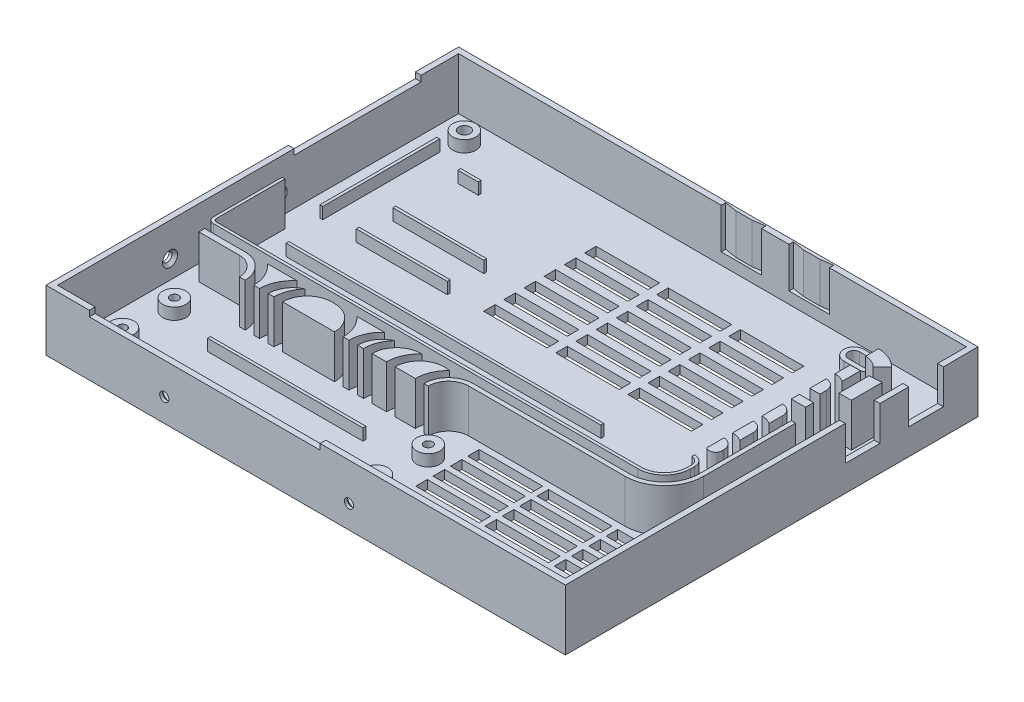
SolidWorks part; units mm, degrees
ref_plane "Front Plane" through (0, 0, 0) normal (0, 0, 1) x (1, 0, 0)
ref_plane "Top Plane" through (0, 0, 0) normal (0, 1, 0) x (1, 0, 0)
ref_plane "Right Plane" through (0, 0, 0) normal (1, 0, 0) x (0, 0, -1)
sketch "Sketch1" plane through (0, 0, 0) normal (0, 1, 0) x (1, 0, 0)
  line L0 (-67.5, 0) -> (67.5, 0) construction
  line L1 (0, 38) -> (0, -38) construction
  line L3 (-67.5, 38) -> (67.5, 38) construction
  line L4 (-67.5, 38) -> (-67.5, -38) construction
  line L5 (-67.5, -38) -> (67.5, -38) construction
  line L6 (67.5, 38) -> (67.5, -38) construction
  line L7 (-67.5, 38) -> (67.5, -38) construction
  line L8 (-67.5, -38) -> (67.5, 38) construction
  line L9 (-71, -71.5) -> (24, -71.5) construction
  line L10 (-23.5, -59) -> (-23.5, -84) construction
  line L11 (-38, -59) -> (-38, -71.5) construction
  line L12 (-17, -59) -> (-17, -71.5) construction
  line L13 (11, -59) -> (11, -71.5) construction
  line L14 (-79.5, 48) -> (-79.5, -95) construction
  line L16 (24, -59) -> (24, -84) construction
  line L17 (-79.5, -95) -> (100.5, -95) construction
  line L18 (100.5, -95) -> (100.5, 48) construction
  line L19 (-71, -59) -> (-71, -84) construction
  line L20 (-71, -84) -> (24, -84) construction
  line L21 (100.5, 48) -> (-79.5, 48) construction
  line L22 (-71, -59) -> (24, -59) construction
  line L23 (0, 38) -> (0, 42) construction
  line L24 (-71.5, 42) -> (71.5, 42) construction
  line L25 (-71.5, 42) -> (-71.5, -42) construction
  line L26 (-71.5, -42) -> (71.5, -42) construction
  line L27 (71.5, 42) -> (71.5, -42) construction
  line L28 (-67.5, 0) -> (-71.5, 0) construction
  line L29 (-43, -59) -> (-43, -71.5) construction
  line L30 (-48, -59) -> (-48, -71.5) construction
  line L31 (-12, -59) -> (-12, -71.5) construction
  line L32 (-7, -59) -> (-7, -71.5) construction
  line L33 (1, -59) -> (1, -71.5) construction
  line L34 (67.5, 38) -> (72.7, 38) construction
  line L35 (67.5, 40) -> (72.7, 40)
  line L36 (67.5, 36) -> (72.7, 36)
  line L37 (67.5, -38) -> (72.6846, -38.4) construction
  line L40 (67.6538, -36.0059) -> (72.8384, -36.4059)
  line L41 (67.3462, -39.9941) -> (72.5307, -40.3941)
  line L42 (-67.5, -38) -> (-67.5, -38.4) construction
  line L43 (-65.5, -38) -> (-65.5, -38.4)
  line L44 (-69.5, -38) -> (-69.5, -38.4)
  circle A0 centre (-67.5, 38) radius 2
  circle A4 centre (-67.5, -62.5) radius 1.5
  circle A8 centre (20.5, -62.5) radius 1.5
  circle A9 centre (20.5, -80.5) radius 1.5
  circle A10 centre (-67.5, -80.5) radius 1.5
  arc A11 (67.5, 40) -> (67.5, 36) centre (67.5, 38) ccw
  arc A12 (72.7, 36) -> (72.7, 40) centre (72.7, 38) ccw
  arc A15 (67.6538, -36.0059) -> (67.3462, -39.9941) centre (67.5, -38) ccw
  arc A16 (72.5307, -40.3941) -> (72.8384, -36.4059) centre (72.6846, -38.4) ccw
  arc A17 (-65.5, -38) -> (-69.5, -38) centre (-67.5, -38) ccw
  arc A18 (-69.5, -38.4) -> (-65.5, -38.4) centre (-67.5, -38.4) ccw
  point P5 (0, 0)
  point P11 (70.1, 38)
  point P13 (-67.5, -38.2)
  point P14 (-23.5, -70)
  point P27 (0, 0)
  point P62 (70.0923, -38.2)
  dimension "D3" = 4
  dimension "D6" = 84
  dimension "D1" = 76
  dimension "D2" = 135
  dimension "D4" = 18
  dimension "D5" = 88
  dimension "D7" = 143
  dimension "D8" = 25
  dimension "D9" = 95
  dimension "D10" = 17
  dimension "D11" = 28
  dimension "D12" = 33
  dimension "D13" = 54
  dimension "D14" = 82
  dimension "D15" = 14.5
  dimension "D16" = 10
  dimension "D17" = 12
  dimension "D18" = 33
  dimension "D19" = 23
  dimension "D20" = 59
  dimension "D21" = 64
  dimension "D22" = 72
  dimension "D23" = 5.2
  dimension "D24" = 4
  dimension "D25" = 4
  dimension "D26" = 5.2
  dimension "D27" = 4
  dimension "D28" = 0.4
  dimension "D29" = 0.4
sketch "CablePath" plane through (0, 0, 0) normal (0, 1, 0) x (1, 0, 0)
  line L0 (-12, -59) -> (-12, -56) construction
  line L5 (101, -94.5) -> (101, 47)
  line L6 (101, 47) -> (-79, 47)
  line L8 (-43, -56) -> (-43, -70.139) construction
  line L9 (-75.5, -42.5222) -> (-75.5, -18.6789) construction
  line L12 (71.5, -29) -> (80.8048, -29) construction
  line L16 (-71.5, -42) -> (71.5, -42) construction
  line L18 (71.5, -18.84) -> (80.8048, -18.84) construction
  line L21 (80.8048, -51.7714) -> (80.8048, 34.0145) construction
  line L22 (30.5, -56) -> (-60.9203, -56) construction
  line L23 (-10.5, -56) -> (-8.5, -56)
  line L24 (71.5, 40.5) -> (71.5, -42) construction
  line L25 (1, -59) -> (1, -56) construction
  line L26 (85.8048, -3.52) -> (85.8048, -35.359) construction
  line L27 (-79, 47) -> (-79, -94.5)
  line L28 (11, -59) -> (11, -56) construction
  line L29 (-79, -94.5) -> (101, -94.5)
  line L30 (-38, -70.139) -> (-38, -56) construction
  line L31 (-43, -59) -> (-43, -71.5) construction
  line L32 (-38, -59) -> (-38, -71.5) construction
  line L33 (71.5, 1.48) -> (80.8048, 1.48) construction
  line L34 (-58, -44.5) -> (-72.0222, -44.5)
  line L35 (75.1637, -46) -> (-33, -46) construction
  line L36 (84.3048, -3.52) -> (84.3048, -8.2028)
  line L37 (-71, -59) -> (24, -59) construction
  line L38 (75.1637, -44.5) -> (-33, -44.5)
  line L39 (71.5, -8.68) -> (80.8048, -8.68) construction
  line L40 (87.3048, -3.52) -> (87.3048, -35.359)
  line L41 (21, -47.5) -> (75.1637, -47.5)
  line L42 (84.3048, -13.68) -> (84.3048, -18.3628)
  line L43 (84.3048, -23.84) -> (84.3048, -24.2165)
  line L44 (84.3048, -3.52) -> (84.3048, -35.359) construction
  line L45 (84.3048, -34) -> (84.3048, -35.359)
  line L46 (-27.8976, -47.4999) -> (-26.899, -47.4999)
  line L47 (75.1637, -47.5) -> (-33, -47.5) construction
  line L48 (2.5, -56) -> (9.5, -56)
  line L49 (-41.5, -56) -> (-39.5, -56)
  line L50 (-36.5, -56) -> (-18.5, -56)
  line L51 (-17, -59) -> (-17, -71.5) construction
  line L52 (21, -49) -> (75.1637, -49)
  line L53 (88.8048, -3.52) -> (88.8048, -35.359)
  line L54 (83.3048, -34) -> (83.3048, -35.359)
  line L55 (75.1637, -43.5) -> (-33, -43.5)
  line L56 (12.5, -56) -> (14, -56)
  line L57 (-58, -46) -> (-72.0222, -46) construction
  line L58 (80.8048, 2.98) -> (80.8048, 5.7849)
  line L59 (80.8048, -0.02) -> (80.8048, -7.18)
  line L60 (80.8048, -10.18) -> (80.8048, -17.34)
  line L61 (80.8048, -20.34) -> (80.8048, -26.2952)
  line L62 (80.8048, -30.5) -> (80.8048, -31.5)
  line L63 (-74, -42.5222) -> (-74, -18.6789)
  line L64 (80.8048, 5.7849) -> (85.7673, 5.7849)
  line L65 (85.7673, 5.7849) -> (85.7673, 2.98)
  line L66 (85.7673, 2.98) -> (80.8048, 2.98)
  line L67 (87.3048, -3.52) -> (88.8048, -3.52)
  line L68 (-7, -59) -> (-7, -56) construction
  line L69 (-17, -59) -> (-17, -56) construction
  line L70 (-48, -59) -> (-48, -56) construction
  line L71 (-58, -43.5) -> (-72.0222, -43.5)
  line L72 (-73, -42.5222) -> (-73, -18.6789)
  line L73 (11, -59) -> (11, -71.5) construction
  line L74 (-58, -47.5) -> (-72.0222, -47.5)
  line L75 (-58, -49.5) -> (-72.0222, -49.5)
  line L76 (-51.5, -56) -> (-49.5, -56)
  line L77 (-72.0222, -47.5) -> (-72.0222, -49.5)
  line L78 (-58, -43.5) -> (-33, -43.5)
  line L79 (-74, -18.6789) -> (-73, -18.6789)
  line L80 (-46.5, -56) -> (-44.5, -56)
  line L81 (-19.2537, -47.5) -> (-9.746, -47.5)
  line L82 (-40.38, -47.1804) -> (-50.62, -47.1804)
  line L83 (-58, -44.5) -> (-33, -44.5)
  line L84 (-15.5, -56) -> (-13.5, -56)
  line L85 (3, -47.5) -> (3.254, -47.5)
  line L86 (-5.5, -56) -> (-0.5, -56)
  line L87 (-71.5, 42) -> (-71.5, -42) construction
  line L88 (67.5, 16.6233) -> (80.8048, 16.6233) construction
  line L89 (67.5, 27.1917) -> (80.8048, 27.1917) construction
  line L90 (67.5, 6.7426) -> (83.9849, 6.7426) construction
  line L91 (85.8048, -3.52) -> (85.8048, 11.6233) construction
  line L92 (85.8048, 11.6233) -> (85.8048, 22.1917) construction
  line L93 (80.8048, 33.1917) -> (80.8048, 28.6917)
  line L94 (85.4191, 26.7697) -> (88.5829, 29.9699)
  line L95 (87.3048, 13.0166) -> (87.3048, 23.4421)
  line L96 (87.3048, 23.4421) -> (91.5804, 23.7236)
  line L97 (84.3065, 23.4421) -> (84.3055, 17.1)
  line L98 (84.3044, 9.4184) -> (80.8048, 9.4184)
  line L99 (80.8048, 9.4184) -> (80.8048, 15.1233)
  line L100 (84.3048, 11.6233) -> (84.3044, 9.4184)
  line L101 (80.8048, 18.1233) -> (80.8048, 23.4421)
  line L102 (91.5804, 23.7236) -> (91.5804, 13.0166)
  line L103 (91.5804, 13.0166) -> (87.3048, 13.0166)
  line L104 (84.3065, 23.4421) -> (80.8048, 23.4421)
  arc A0 (14, -56) -> (21, -49) centre (21, -56) cw
  circle A1 centre (-67.5, -62.5) radius 1.5 construction
  arc A2 (9.5, -56) -> (21, -44.5) centre (21, -56) cw construction
  arc A3 (75.1637, -49) -> (88.8048, -35.359) centre (75.1637, -35.359) ccw
  arc A4 (85.4191, 26.7697) -> (80.8048, 28.6917) centre (80.8048, 22.1917) ccw
  arc A5 (88.5829, 29.9699) -> (80.8048, 33.1917) centre (80.8048, 22.1917) ccw
  arc A7 (84.3055, 17.1) -> (80.8048, 18.1233) centre (80.8048, 11.6233) ccw
  circle A8 centre (-67.5, -80.5) radius 1.5 construction
  circle A9 centre (-67.5, -62.5) radius 1.5
  circle A10 centre (20.5, -62.5) radius 1.5 construction
  circle A11 centre (-67.5, -80.5) radius 1.5
  arc A12 (80.8048, -26.2952) -> (84.3048, -24.2165) centre (82.1448, -24.5655) ccw
  arc A13 (85.8048, 22.1917) -> (80.8048, 27.1917) centre (80.8048, 22.1917) ccw construction
  arc A14 (85.8048, 11.6233) -> (80.8048, 16.6233) centre (80.8048, 11.6233) ccw construction
  arc A15 (84.3048, 11.6233) -> (80.8048, 15.1233) centre (80.8048, 11.6233) ccw
  arc A16 (80.8048, 1.48) -> (85.8048, -3.52) centre (80.8048, -3.52) cw construction
  arc A17 (80.8048, -8.68) -> (85.8048, -13.68) centre (80.8048, -13.68) cw construction
  arc A18 (80.8048, -18.84) -> (85.8048, -23.84) centre (80.8048, -23.84) cw construction
  arc A19 (80.8048, -29) -> (85.8048, -34) centre (80.8048, -34) cw construction
  arc A20 (75.1637, -46) -> (85.8048, -35.359) centre (75.1637, -35.359) ccw construction
  arc A21 (-43, -56) -> (-33, -46) centre (-33, -56) cw construction
  arc A22 (-38, -56) -> (-27.8796, -46) centre (-27.9993, -56) cw construction
  arc A23 (1, -56) -> (11, -46) centre (11, -56) cw construction
  arc A24 (11, -56) -> (21, -46) centre (21, -56) cw construction
  circle A25 centre (20.5, -62.5) radius 1.5
  circle A26 centre (20.5, -80.5) radius 1.5 construction
  circle A27 centre (20.5, -80.5) radius 1.5
  arc A28 (80.8048, -0.02) -> (84.3048, -3.52) centre (80.8048, -3.52) cw
  arc A29 (75.1637, -44.5) -> (84.3048, -35.359) centre (75.1637, -35.359) ccw
  arc A30 (-44.5, -56) -> (-40.38, -47.1804) centre (-33, -56) cw
  arc A31 (80.8048, -10.18) -> (84.3048, -13.68) centre (80.8048, -13.68) cw
  arc A32 (80.8048, -20.34) -> (84.3048, -23.84) centre (80.8048, -23.84) cw
  arc A33 (80.8048, -30.5) -> (84.3048, -34) centre (80.8048, -34) cw
  arc A34 (12.5, -56) -> (21, -47.5) centre (21, -56) cw
  arc A35 (2.5, -56) -> (13, -47.7386) centre (11, -56) cw
  arc A36 (-36.5, -56) -> (-27.8976, -47.4999) centre (-27.9993, -56) cw
  arc A37 (80.8048, 2.98) -> (87.3048, -3.52) centre (80.8048, -3.52) cw construction
  arc A38 (75.1637, -47.5) -> (87.3048, -35.359) centre (75.1637, -35.359) ccw
  arc A39 (-41.5, -56) -> (-36.5004, -48.2542) centre (-33, -56) cw
  arc A40 (80.8048, -7.18) -> (84.3048, -8.2028) centre (80.8048, -13.68) cw
  arc A41 (80.8048, -17.34) -> (84.3048, -18.3628) centre (80.8048, -23.84) cw
  arc A43 (9.5, -56) -> (13, -47.7386) centre (21, -56) cw
  arc A44 (-0.5, -56) -> (3.254, -47.5) centre (11, -56) cw
  arc A45 (-39.5, -56) -> (-36.5004, -48.2542) centre (-27.9993, -56) cw
  arc A46 (-39.5, -56) -> (-27.8617, -44.5001) centre (-27.9993, -56) cw construction
  arc A47 (87.3048, 11.6233) -> (80.8048, 18.1233) centre (80.8048, 11.6233) ccw construction
  arc A48 (80.8048, -7.18) -> (87.3048, -13.68) centre (80.8048, -13.68) cw construction
  arc A49 (80.8048, -17.34) -> (87.3048, -23.84) centre (80.8048, -23.84) cw construction
  arc A50 (80.8048, 4.48) -> (88.8048, -3.52) centre (80.8048, -3.52) cw construction
  arc A51 (-0.5, -56) -> (11, -44.5) centre (11, -56) cw construction
  arc A52 (80.8048, -31.5) -> (83.3048, -34) centre (80.8048, -34) cw
  arc A53 (75.1637, -43.5) -> (83.3048, -35.359) centre (75.1637, -35.359) ccw
  arc A54 (-48, -56) -> (-58, -46) centre (-58, -56) ccw construction
  arc A55 (-17, -56) -> (-26.881, -46) centre (-27.0007, -56) ccw construction
  arc A56 (-41.5, -56) -> (-33, -47.5) centre (-33, -56) cw construction
  arc A57 (-45.5, -56) -> (-33, -43.5) centre (-33, -56) cw construction
  arc A58 (-72.0222, -46) -> (-75.5, -42.5222) centre (-72.0222, -42.5222) cw construction
  arc A59 (-46.5, -56) -> (-50.62, -47.1804) centre (-58, -56) ccw
  arc A60 (-72.0222, -44.5) -> (-74, -42.5222) centre (-72.0222, -42.5222) cw
  arc A61 (-15.5, -56) -> (-19.2537, -47.5) centre (-27.0007, -56) ccw
  arc A62 (-72.0222, -43.5) -> (-73, -42.5222) centre (-72.0222, -42.5222) cw
  arc A63 (-49.5, -56) -> (-58, -47.5) centre (-58, -56) ccw
  arc A64 (-51.5, -56) -> (-58, -49.5) centre (-58, -56) ccw
  arc A65 (-45.5, -56) -> (-58, -43.5) centre (-58, -56) ccw construction
  arc A66 (-18.5, -56) -> (-26.899, -47.4999) centre (-27.0007, -56) ccw
  arc A67 (-12, -56) -> (-2, -46) centre (-2, -56) cw construction
  arc A68 (-15.5, -56) -> (-26.8631, -44.5001) centre (-27.0007, -56) ccw construction
  arc A69 (-46.5, -56) -> (-58, -44.5) centre (-58, -56) ccw construction
  arc A70 (-44.5, -56) -> (-33, -44.5) centre (-33, -56) cw construction
  arc A71 (2.5, -56) -> (11, -47.5) centre (11, -56) cw construction
  arc A72 (-7, -56) -> (3, -46) centre (3, -56) cw construction
  arc A73 (-10.5, -56) -> (-5.5, -48.254) centre (-2, -56) cw
  arc A74 (-5.5, -56) -> (3, -47.5) centre (3, -56) cw
  arc A75 (-13.5, -56) -> (-9.746, -47.5) centre (-2, -56) cw
  arc A76 (-8.5, -56) -> (-5.5, -48.254) centre (3, -56) cw
  arc A77 (87.3048, 22.1917) -> (80.8048, 28.6917) centre (80.8048, 22.1917) ccw construction
  arc A78 (-13.5, -56) -> (-2, -44.5) centre (-2, -56) cw construction
  arc A79 (-10.5, -56) -> (-2, -47.5) centre (-2, -56) cw construction
  arc A80 (91.8048, 22.1917) -> (80.8048, 33.1917) centre (80.8048, 22.1917) ccw construction
  arc A81 (-8.5, -56) -> (3, -44.5) centre (3, -56) cw construction
  point P0 (67.5, -38)
  point P7 (67.5, 38)
  point P10 (-67.5, -80.5)
  point P117 (77.6351, -51.5)
  point P118 (-14.035, -51.5)
  point P127 (77.6351, -54.5)
  point P128 (-14.035, -54.5)
  point P132 (79.6209, -33.364)
  point P134 (85.4849, -33.364)
  point P137 (3.3488, -47.5)
  point P138 (3.3488, -61)
  point P139 (-10.1512, -61)
  point P146 (3.3488, -50.5)
  point P147 (3.3488, -61)
  point P148 (-7.1512, -61)
  point P154 (80.8048, 22.2244)
  point P242 (3.4721, -55.4721)
  point P243 (-8, -55.4721)
  point P244 (3.4721, -44)
  point P253 (87.3048, 22.2244)
  point P256 (80.8048, 22.2244)
  point P257 (91.8048, 22.2244)
  dimension "D5" = 10.16
  dimension "D8" = 3
  dimension "D23" = 1.5
  dimension "D24" = 5
  dimension "D25" = 5
  dimension "D1" = 1.5
  dimension "D3" = 4
  dimension "D4" = 13
  dimension "D6" = 10.16
  dimension "D7" = 10.16
  dimension "D9" = 3.5
  dimension "D10" = 1.5
  dimension "D11" = 1.5
  dimension "D12" = 1
  dimension "D13" = 1.5
  dimension "D14" = 1
  dimension "D15" = 1.5
  dimension "D16" = 2
  dimension "D17" = 1.5
  dimension "D18" = 1.5
  dimension "D28" = 180
  dimension "D19" = 1.5
  dimension "D20" = 1.5
  dimension "D21" = 1.5
  dimension "D22" = 1.5
  dimension "D26" = 1.5
  dimension "D27" = 6
  dimension "D30" = 1.5
  dimension "D31" = 1.5
sketch "Bottom" plane through (0, 0, 0) normal (0, 1, 0) x (1, 0, 0)
  line L0 (-79.5, 48) -> (-79.5, -95) construction
  line L1 (-79.5, 48) -> (-79.5, -95)
  line L2 (-79.5, -95) -> (100.5, -95) construction
  line L3 (-79.5, -95) -> (100.5, -95)
  line L4 (67.6538, -36.0059) -> (72.8384, -36.4059) construction
  line L5 (67.3462, -39.9941) -> (72.5307, -40.3941) construction
  line L6 (100.5, -95) -> (100.5, 48) construction
  line L7 (100.5, -95) -> (100.5, 48)
  line L8 (100.5, 48) -> (-79.5, 48) construction
  line L9 (100.5, 48) -> (-79.5, 48)
  line L10 (67.6538, -36.0059) -> (72.8384, -36.4059)
  line L11 (67.3462, -39.9941) -> (72.5307, -40.3941)
  line L12 (67.5, 36) -> (72.7, 36) construction
  line L13 (67.5, 40) -> (72.7, 40) construction
  line L14 (67.5, 36) -> (72.7, 36)
  line L15 (67.5, 40) -> (72.7, 40)
  line L16 (-65.5, -38) -> (-65.5, -38.4) construction
  line L17 (-69.5, -38) -> (-69.5, -38.4) construction
  line L18 (-65.5, -38) -> (-65.5, -38.4)
  line L19 (-69.5, -38) -> (-69.5, -38.4)
  arc A0 (72.5307, -40.3941) -> (72.8384, -36.4059) centre (72.6846, -38.4) ccw construction
  arc A1 (67.6538, -36.0059) -> (67.3462, -39.9941) centre (67.5, -38) ccw construction
  arc A2 (72.5307, -40.3941) -> (72.8384, -36.4059) centre (72.6846, -38.4) ccw
  arc A3 (67.6538, -36.0059) -> (67.3462, -39.9941) centre (67.5, -38) ccw
  arc A4 (72.7, 36) -> (72.7, 40) centre (72.7, 38) ccw construction
  arc A5 (67.5, 40) -> (67.5, 36) centre (67.5, 38) ccw construction
  arc A6 (72.7, 36) -> (72.7, 40) centre (72.7, 38) ccw
  arc A7 (67.5, 40) -> (67.5, 36) centre (67.5, 38) ccw
  circle A8 centre (-67.5, 38) radius 2 construction
  circle A9 centre (-67.5, 38) radius 2
  arc A10 (-69.5, -38.4) -> (-65.5, -38.4) centre (-67.5, -38.4) ccw construction
  arc A11 (-65.5, -38) -> (-69.5, -38) centre (-67.5, -38) ccw construction
  arc A12 (-69.5, -38.4) -> (-65.5, -38.4) centre (-67.5, -38.4) ccw
  arc A13 (-65.5, -38) -> (-69.5, -38) centre (-67.5, -38) ccw
  dimension "D1" = 143
  dimension "D2" = 180
extrude "Boss-Bottom" add sketch "Bottom" along normal blind 3
sketch "PCBmount" plane through (0, 3, 0) normal (0, 1, 0) x (1, 0, 0)
  line L0 (-49.5761, -67.9069) -> (-49.5761, -68.9069)
  line L1 (-49.5761, -67.9069) -> (4.2504, -67.9069)
  line L2 (-49.5761, -68.9069) -> (4.2504, -68.9069)
  line L3 (4.2504, -67.9069) -> (4.2504, -68.9069)
  line L5 (-64.5007, -25.8146) -> (44.6202, -25.8146)
  line L6 (-64.5007, -25.8146) -> (-64.5007, -26.8146)
  line L7 (44.6202, -25.8146) -> (44.6202, -26.8146)
  line L8 (-64.5007, -26.8146) -> (44.6202, -26.8146)
  line L9 (-56.6714, -10.3272) -> (-25.1095, -10.3272)
  line L10 (-56.6714, -10.3272) -> (-56.6714, -9.3272)
  line L11 (-25.1095, -10.3272) -> (-25.1095, -9.3272)
  line L12 (-56.6714, -9.3272) -> (-25.1095, -9.3272)
  line L13 (-56.6714, 2.3448) -> (-25.1095, 2.3448)
  line L14 (-56.6714, 2.3448) -> (-56.6714, 3.3448)
  line L15 (-25.1095, 2.3448) -> (-25.1095, 3.3448)
  line L16 (-56.6714, 3.3448) -> (-25.1095, 3.3448)
  line L17 (-70.1846, -9.4098) -> (-69.1846, -9.4098)
  line L18 (-70.1846, -9.4098) -> (-70.1846, 31.1536)
  line L19 (-69.1846, -9.4098) -> (-69.1846, 31.1536)
  line L20 (-70.1846, 31.1536) -> (-69.1846, 31.1536)
  line L21 (-56.6714, 24.8918) -> (-49.5761, 24.8918)
  line L22 (-56.6714, 24.8918) -> (-56.6714, 25.8918)
  line L23 (-49.5761, 24.8918) -> (-49.5761, 25.8918)
  line L24 (-56.6714, 25.8918) -> (-49.5761, 25.8918)
  line L30 (67.5, 36) -> (72.7, 36) construction
  line L31 (67.5, 40) -> (72.7, 40) construction
  line L32 (-67.5, 0) -> (67.5, 0) construction
  line L33 (-67.5, 0) -> (67.5, 0) construction
  line L34 (67.5, 36) -> (72.7, 36)
  line L35 (67.5, 40) -> (72.7, 40)
  line L38 (-65.5, -38) -> (-65.5, -38.4) construction
  line L39 (-69.5, -38) -> (-69.5, -38.4) construction
  line L40 (-65.5, -38) -> (-65.5, -38.4)
  line L41 (-69.5, -38) -> (-69.5, -38.4)
  line L42 (-64, -38) -> (-64, -38.4)
  line L43 (-71, -38) -> (-71, -38.4)
  line L44 (67.5, 34.5) -> (72.7, 34.5)
  line L45 (67.5, 41.5) -> (72.7, 41.5)
  line L46 (67.6538, -36.0059) -> (72.8384, -36.4059) construction
  line L47 (67.3462, -39.9941) -> (72.5307, -40.3941) construction
  line L48 (67.6538, -36.0059) -> (72.8384, -36.4059)
  line L49 (67.3462, -39.9941) -> (72.5307, -40.3941)
  line L50 (67.7692, -34.5104) -> (72.9538, -34.9104)
  line L51 (67.2308, -41.4896) -> (72.4154, -41.8896)
  circle A4 centre (-67.5, -62.5) radius 1.5 construction
  circle A6 centre (-67.5, 38) radius 2 construction
  circle A8 centre (20.5, -80.5) radius 1.5 construction
  circle A9 centre (20.5, -62.5) radius 1.5 construction
  arc A10 (72.7, 36) -> (72.7, 40) centre (72.7, 38) ccw construction
  circle A11 centre (-67.5, -80.5) radius 1.5 construction
  circle A12 centre (-67.5, -62.5) radius 1.5
  arc A13 (-65.5, -38) -> (-69.5, -38) centre (-67.5, -38) ccw construction
  circle A14 centre (-67.5, 38) radius 2
  circle A16 centre (-67.5, 38) radius 4
  arc A17 (67.5, 40) -> (67.5, 36) centre (67.5, 38) ccw construction
  arc A18 (72.7, 36) -> (72.7, 40) centre (72.7, 38) ccw
  arc A19 (-69.5, -38.4) -> (-65.5, -38.4) centre (-67.5, -38.4) ccw construction
  circle A20 centre (-67.5, -62.5) radius 4
  circle A21 centre (-67.5, -80.5) radius 4
  circle A22 centre (20.5, -80.5) radius 4
  circle A23 centre (20.5, -62.5) radius 4
  circle A24 centre (-67.5, -80.5) radius 1.5
  circle A25 centre (20.5, -80.5) radius 1.5
  circle A26 centre (20.5, -62.5) radius 1.5
  arc A27 (67.5, 40) -> (67.5, 36) centre (67.5, 38) ccw
  arc A30 (-65.5, -38) -> (-69.5, -38) centre (-67.5, -38) ccw
  arc A31 (-69.5, -38.4) -> (-65.5, -38.4) centre (-67.5, -38.4) ccw
  arc A32 (-71, -38.4) -> (-64, -38.4) centre (-67.5, -38.4) ccw
  arc A33 (-64, -38) -> (-71, -38) centre (-67.5, -38) ccw
  arc A34 (72.7, 34.5) -> (72.7, 41.5) centre (72.7, 38) ccw
  arc A35 (67.5, 41.5) -> (67.5, 34.5) centre (67.5, 38) ccw
  arc A36 (72.5307, -40.3941) -> (72.8384, -36.4059) centre (72.6846, -38.4) ccw construction
  arc A37 (67.6538, -36.0059) -> (67.3462, -39.9941) centre (67.5, -38) ccw construction
  arc A38 (72.5307, -40.3941) -> (72.8384, -36.4059) centre (72.6846, -38.4) ccw
  arc A39 (67.6538, -36.0059) -> (67.3462, -39.9941) centre (67.5, -38) ccw
  arc A40 (72.4154, -41.8896) -> (72.9538, -34.9104) centre (72.6846, -38.4) ccw
  arc A41 (67.7692, -34.5104) -> (67.2308, -41.4896) centre (67.5, -38) ccw
  dimension "D1" = 8
  dimension "D2" = 8
  dimension "D3" = 1
  dimension "D5" = 1.5
  dimension "D6" = 1.5
  dimension "D4" = 1.5
extrude "Boss-PCBmount" add sketch "PCBmount" along normal blind 4
sketch "Sides" plane through (0, 3, 0) normal (0, 1, 0) x (1, 0, 0)
  line L0 (-79.5, -95) -> (100.5, -95) construction
  line L1 (100.5, -95) -> (100.5, 48) construction
  line L2 (-79.5, 48) -> (-79.5, -95) construction
  line L3 (100.5, 48) -> (-79.5, 48) construction
  line L4 (-79.5, -95) -> (100.5, -95)
  line L5 (100.5, -95) -> (100.5, 48)
  line L6 (-79.5, 48) -> (-79.5, -95)
  line L7 (100.5, 48) -> (-79.5, 48)
  line L8 (-77.5, -93) -> (98.5, -93)
  line L9 (98.5, -93) -> (98.5, 46)
  line L10 (98.5, 46) -> (-77.5, 46)
  line L11 (-77.5, 46) -> (-77.5, -93)
  dimension "D1" = 2
extrude "Boss-Sides" add sketch "Sides" along normal blind 18
sketch "24VHeatBed" plane through (100.5, 0, 0) normal (1, 0, 0) x (0, 0, -1)
  line L0 (36, 21) -> (36, 9)
  line L1 (48, 21) -> (48, 0) construction
  line L2 (36, 9) -> (24, 9)
  line L3 (24, 9) -> (24, 21)
  line L4 (24, 21) -> (36, 21)
  line L5 (14, 21) -> (14, 9)
  line L6 (14, 9) -> (2, 9)
  line L7 (2, 9) -> (2, 21)
  line L8 (2, 21) -> (14, 21)
  line L10 (-95, 21) -> (48, 21) construction
  dimension "D3" = 12
  dimension "D5" = 12
  dimension "D6" = 10
extrude "Cut-24VHeatBed" cut sketch "24VHeatBed" against normal up to surface (2 mm away) up to face at (98.5, 12, 23.5)
extrude "Boss-CablePath" add sketch "CablePath" along normal blind 18 contours A74 L85 A44 L86 | A76 A73 L23 | A75 L81 A61 L84 | L38 L83 L34 A60 L63 L79 L72 A62 L71 L78 L55 A53 L54 A52 L62 A33 L45 A29 | A66 L46 A36 L50 | A35 A43 L48 | A34 L41 A38 L40 L67 L53 A3 L52 A0 L56 | L75 L77 L74 A63 L76 A64 | A59 L82 A30 L80 | A39 A45 L49 | L43 A12 L61 A32 | L42 A41 L60 A31 | L36 A40 L59 A28 | L65 L66 L58 L64 | L100 L98 L99 A15 | L97 A7 L101 L104 | L93 A4 L94 A5 | L102 L103 L95 L96
sketch "Fan" plane through (0, 3, 0) normal (0, 1, 0) x (1, 0, 0)
  line L1 (55.5, -50) -> (95.5, -50) construction
  line L2 (55.5, -50) -> (55.5, -90) construction
  line L3 (55.5, -90) -> (95.5, -90) construction
  line L4 (95.5, -50) -> (95.5, -90) construction
  line L5 (55.5, -50) -> (95.5, -90) construction
  line L6 (55.5, -90) -> (95.5, -50) construction
  line L8 (98.5, -93) -> (98.5, 2) construction
  line L9 (-77.5, -93) -> (98.5, -93) construction
  circle A0 centre (75.5, -70) radius 19
  circle A1 centre (75.5, -70) radius 10
  arc A2 (75.5, -70) -> (75.5, -51) centre (80.3261, -60.5) cw
  arc A3 (75.5, -70) -> (91.9545, -60.5) centre (86.1403, -69.4295) cw
  arc A4 (75.5, -70) -> (91.9545, -79.5) centre (81.3142, -78.9295) cw
  arc A5 (75.5, -70) -> (75.5, -89) centre (70.6739, -79.5) cw
  arc A6 (75.5, -70) -> (59.0455, -79.5) centre (64.8597, -70.5705) cw
  arc A7 (75.5, -70) -> (59.0455, -60.5) centre (69.6858, -61.0705) cw
  point P0 (75.5, -70)
  point P27 (75.5, -70)
  dimension "D5" = 38
  dimension "D6" = 20
  dimension "D1" = 40
  dimension "D2" = 40
  dimension "D3" = 3
  dimension "D4" = 3
  dimension "D7" = 6
sketch "FanHoles" plane through (0, 0, 0) normal (0, -1, 0) x (1, 0, 0)
  line L0 (55.5, 90) -> (95.5, 50) construction
  line L1 (55.5, 90) -> (95.5, 50) construction
  line L2 (55.5, 50) -> (95.5, 90) construction
  line L3 (55.5, 50) -> (95.5, 90) construction
  line L4 (55.5, 50) -> (95.5, 50) construction
  line L5 (55.5, 50) -> (95.5, 50) construction
  line L6 (55.5, 90) -> (95.5, 90) construction
  line L7 (55.5, 90) -> (95.5, 90) construction
  line L8 (55.5, 50) -> (55.5, 90) construction
  line L9 (55.5, 50) -> (55.5, 90) construction
  line L10 (95.5, 50) -> (95.5, 90) construction
  line L11 (95.5, 50) -> (95.5, 90) construction
  line L12 (75.5, 50) -> (75.5, 90) construction
  line L13 (55.5, 70) -> (95.5, 70) construction
  circle A1 centre (59.5, 54) radius 1.5
  circle A2 centre (59.5, 86) radius 1.5
  circle A6 centre (91.5, 86) radius 1.5
  circle A7 centre (91.5, 54) radius 1.5
  dimension "D1" = 32
  dimension "D2" = 32
sketch "ExtruderCables" plane through (0, 0, 95) normal (0, 0, 1) x (1, 0, 0)
  line L0 (-79.5, 21) -> (-79.5, 0) construction
  line L1 (-64.5, 21) -> (15.5, 21)
  line L2 (-64.5, 21) -> (-64.5, 19)
  line L3 (-64.5, 19) -> (15.5, 19)
  line L4 (15.5, 21) -> (15.5, 19)
  line L5 (-64.5, 21) -> (15.5, 19) construction
  line L6 (-64.5, 19) -> (15.5, 21) construction
  line L7 (-79.5, 21) -> (100.5, 21) construction
  point P0 (-24.5, 20)
  dimension "D1" = 15
  dimension "D2" = 80
extrude "Cut-ExtruderCables" cut sketch "ExtruderCables" against normal up to surface (2 mm away) up to face at (10.5, 12, 93)
sketch "LCD" plane through (-79.5, 0, 0) normal (-1, 0, 0) x (0, 0, 1)
  line L0 (-33, 21) -> (-33, 19)
  line L1 (-33, 21) -> (11, 21)
  line L2 (-33, 19) -> (11, 19)
  line L3 (11, 21) -> (11, 19)
  line L4 (-48, 21) -> (95, 21) construction
  line L5 (-48, 21) -> (-48, 0) construction
  dimension "D1" = 15
  dimension "D2" = 59
extrude "Cut-LCD" cut sketch "LCD" against normal up to surface (2 mm away) up to face at (-77.5, 12, 23.5)
sketch "Sketch2" plane through (0, 0, 0) normal (0, -1, 0) x (1, 0, 0)
  line L0 (-79.5, -48) -> (-79.5, 95) construction
  line L3 (-79.5, 95) -> (100.5, 95) construction
  line L4 (35.5, 123) -> (35.5, 95)
  line L5 (-98.5, -48) -> (-98.5, 143.5262) construction
  line L6 (-104.4968, 114) -> (115.2818, 114) construction
  line L7 (35.5, 123) -> (-48.5, 123)
  line L8 (-107.5, 64) -> (-107.5, 6)
  line L9 (35.5, 95) -> (-48.5, 95)
  line L10 (-79.5, 64) -> (-79.5, 6)
  line L11 (-48.5, 95) -> (-48.5, 123)
  line L13 (-79.5, 6) -> (-107.5, 6)
  line L14 (-107.5, 64) -> (-79.5, 64)
  line L15 (-79.5, 95) -> (-79.5, 123) construction
  line L16 (-79.5, 95) -> (-116.8086, 95) construction
  line L17 (-107.5, 95) -> (-107.5, 123) construction
  line L18 (-107.5, 123) -> (-79.5, 123) construction
  circle A0 centre (-98.5, 16) radius 2.5
  circle A1 centre (-98.5, 54) radius 2.5
  circle A2 centre (-38.5, 114) radius 2.5
  circle A3 centre (25.5, 114) radius 2.5
  dimension "D2" = 28
  dimension "D4" = 60
  dimension "D5" = 60
  dimension "D12" = 10
  dimension "D3" = 38
  dimension "D6" = 64
  dimension "D7" = 28
  dimension "D8" = 9
  dimension "D9" = 9
  dimension "D10" = 10
  dimension "D11" = 10
  dimension "D13" = 10
sketch "USB" plane through (0, 21, 0) normal (0, 1, 0) x (1, 0, 0)
  line L0 (37, 46) -> (51, 46)
  line L1 (98.5, 46) -> (-77.5, 46) construction
  line L2 (51, 46) -> (51, 47.4707)
  line L3 (4.6819, 46.8766) -> (57.5762, 46.8766) construction
  line L4 (13.5, 47.5631) -> (17.6913, 46.8766)
  line L5 (37, 47.5631) -> (41.1913, 46.8766)
  line L6 (37, 47.5631) -> (37, 46)
  line L7 (100.5, 36) -> (100.5, 48) construction
  line L8 (27.5, 46) -> (13.5, 46)
  line L9 (13.5, 46) -> (13.5, 47.5631)
  line L10 (27.5, 47.5504) -> (23.3067, 46.8766)
  line L11 (51, 47.4707) -> (46.7946, 46.8766)
  line L12 (17.6913, 46.8766) -> (23.3067, 46.8766)
  line L13 (27.5, 47.5504) -> (27.5, 46)
  line L14 (41.1913, 46.8766) -> (46.7946, 46.8766)
  dimension "D1" = 14
  dimension "D2" = 49.5
  dimension "D3" = 73
extrude "Cut-USB" cut sketch "USB" against normal blind 14
sketch "AirOut" plane through (0, 3, 0) normal (0, 1, 0) x (1, 0, 0)
  line L0 (50.8814, -87.2405) -> (72.8814, -87.2405)
  line L1 (74.8814, -87.2405) -> (96.8814, -87.2405)
  line L2 (74.8814, -87.2405) -> (74.8814, -91.2405)
  line L3 (74.8814, -91.2405) -> (96.8814, -91.2405)
  line L4 (96.8814, -87.2405) -> (96.8814, -91.2405)
  line L5 (74.8814, -87.2405) -> (96.8814, -91.2405) construction
  line L6 (74.8814, -91.2405) -> (96.8814, -87.2405) construction
  line L7 (50.8814, -87.2405) -> (50.8814, -91.2405)
  line L8 (50.8814, -91.2405) -> (72.8814, -91.2405)
  line L9 (72.8814, -87.2405) -> (72.8814, -91.2405)
  line L10 (26.8814, -87.2405) -> (48.8814, -87.2405)
  line L11 (26.8814, -87.2405) -> (26.8814, -91.2405)
  line L12 (26.8814, -91.2405) -> (48.8814, -91.2405)
  line L13 (48.8814, -87.2405) -> (48.8814, -91.2405)
  line L14 (50.8814, -81.2405) -> (72.8814, -81.2405)
  line L15 (50.8814, -81.2405) -> (50.8814, -85.2405)
  line L16 (50.8814, -85.2405) -> (72.8814, -85.2405)
  line L17 (72.8814, -81.2405) -> (72.8814, -85.2405)
  line L18 (26.8814, -81.2405) -> (48.8814, -81.2405)
  line L19 (26.8814, -81.2405) -> (26.8814, -85.2405)
  line L20 (26.8814, -85.2405) -> (48.8814, -85.2405)
  line L21 (48.8814, -81.2405) -> (48.8814, -85.2405)
  line L22 (50.8814, -75.2405) -> (72.8814, -75.2405)
  line L23 (50.8814, -75.2405) -> (50.8814, -79.2405)
  line L24 (50.8814, -79.2405) -> (72.8814, -79.2405)
  line L25 (72.8814, -75.2405) -> (72.8814, -79.2405)
  line L26 (26.8814, -75.2405) -> (48.8814, -75.2405)
  line L27 (26.8814, -75.2405) -> (26.8814, -79.2405)
  line L28 (26.8814, -79.2405) -> (48.8814, -79.2405)
  line L29 (48.8814, -75.2405) -> (48.8814, -79.2405)
  line L30 (50.8814, -69.2405) -> (72.8814, -69.2405)
  line L31 (50.8814, -69.2405) -> (50.8814, -73.2405)
  line L32 (50.8814, -73.2405) -> (72.8814, -73.2405)
  line L33 (72.8814, -69.2405) -> (72.8814, -73.2405)
  line L34 (26.8814, -69.2405) -> (48.8814, -69.2405)
  line L35 (26.8814, -69.2405) -> (26.8814, -73.2405)
  line L36 (26.8814, -73.2405) -> (48.8814, -73.2405)
  line L37 (48.8814, -69.2405) -> (48.8814, -73.2405)
  line L38 (50.8814, -63.2405) -> (72.8814, -63.2405)
  line L39 (50.8814, -63.2405) -> (50.8814, -67.2405)
  line L40 (50.8814, -67.2405) -> (72.8814, -67.2405)
  line L41 (72.8814, -63.2405) -> (72.8814, -67.2405)
  line L42 (26.8814, -63.2405) -> (48.8814, -63.2405)
  line L43 (26.8814, -63.2405) -> (26.8814, -67.2405)
  line L44 (26.8814, -67.2405) -> (48.8814, -67.2405)
  line L45 (48.8814, -63.2405) -> (48.8814, -67.2405)
  line L46 (74.8814, -81.2405) -> (96.8814, -81.2405)
  line L47 (74.8814, -81.2405) -> (74.8814, -85.2405)
  line L48 (74.8814, -85.2405) -> (96.8814, -85.2405)
  line L49 (96.8814, -81.2405) -> (96.8814, -85.2405)
  line L50 (74.8814, -75.2405) -> (96.8814, -75.2405)
  line L51 (74.8814, -75.2405) -> (74.8814, -79.2405)
  line L52 (74.8814, -79.2405) -> (96.8814, -79.2405)
  line L53 (96.8814, -75.2405) -> (96.8814, -79.2405)
  line L54 (74.8814, -69.2405) -> (96.8814, -69.2405)
  line L55 (74.8814, -69.2405) -> (74.8814, -73.2405)
  line L56 (74.8814, -73.2405) -> (96.8814, -73.2405)
  line L57 (96.8814, -69.2405) -> (96.8814, -73.2405)
  line L58 (74.8814, -63.2405) -> (96.8814, -63.2405)
  line L59 (74.8814, -63.2405) -> (74.8814, -67.2405)
  line L60 (74.8814, -67.2405) -> (96.8814, -67.2405)
  line L61 (96.8814, -63.2405) -> (96.8814, -67.2405)
  line L62 (74.8814, -57.2405) -> (96.8814, -57.2405)
  line L63 (74.8814, -57.2405) -> (74.8814, -61.2405)
  line L64 (74.8814, -61.2405) -> (96.8814, -61.2405)
  line L65 (96.8814, -57.2405) -> (96.8814, -61.2405)
  line L66 (50.8814, -57.2405) -> (72.8814, -57.2405)
  line L67 (50.8814, -57.2405) -> (50.8814, -61.2405)
  line L68 (50.8814, -61.2405) -> (72.8814, -61.2405)
  line L69 (72.8814, -57.2405) -> (72.8814, -61.2405)
  line L70 (26.8814, -57.2405) -> (48.8814, -57.2405)
  line L71 (26.8814, -57.2405) -> (26.8814, -61.2405)
  line L72 (26.8814, -61.2405) -> (48.8814, -61.2405)
  line L73 (48.8814, -57.2405) -> (48.8814, -61.2405)
  line L74 (74.8814, -51.2405) -> (96.8814, -51.2405)
  line L75 (74.8814, -51.2405) -> (74.8814, -55.2405)
  line L76 (74.8814, -55.2405) -> (96.8814, -55.2405)
  line L77 (96.8814, -51.2405) -> (96.8814, -55.2405)
  line L78 (50.8814, -51.2405) -> (72.8814, -51.2405)
  line L79 (50.8814, -51.2405) -> (50.8814, -55.2405)
  line L80 (50.8814, -55.2405) -> (72.8814, -55.2405)
  line L81 (72.8814, -51.2405) -> (72.8814, -55.2405)
  line L82 (26.8814, -51.2405) -> (48.8814, -51.2405)
  line L83 (26.8814, -51.2405) -> (26.8814, -55.2405)
  line L84 (26.8814, -55.2405) -> (48.8814, -55.2405)
  line L85 (48.8814, -51.2405) -> (48.8814, -55.2405)
  line L86 (11.148, 26.0057) -> (33.148, 26.0057)
  line L87 (-13.852, 30.0057) -> (8.148, 30.0057)
  line L88 (-13.852, 30.0057) -> (-13.852, 26.0057)
  line L89 (-13.852, 26.0057) -> (8.148, 26.0057)
  line L90 (8.148, 30.0057) -> (8.148, 26.0057)
  line L91 (-13.852, 30.0057) -> (8.148, 26.0057) construction
  line L92 (-13.852, 26.0057) -> (8.148, 30.0057) construction
  line L93 (11.148, 30.0057) -> (33.148, 30.0057)
  line L94 (33.148, 30.0057) -> (33.148, 26.0057)
  line L95 (11.148, 30.0057) -> (11.148, 26.0057)
  line L96 (36.148, 26.0057) -> (58.148, 26.0057)
  line L97 (36.148, 30.0057) -> (58.148, 30.0057)
  line L98 (58.148, 30.0057) -> (58.148, 26.0057)
  line L99 (36.148, 30.0057) -> (36.148, 26.0057)
  line L100 (11.148, 19.0057) -> (33.148, 19.0057)
  line L101 (11.148, 23.0057) -> (33.148, 23.0057)
  line L102 (33.148, 23.0057) -> (33.148, 19.0057)
  line L103 (11.148, 23.0057) -> (11.148, 19.0057)
  line L104 (36.148, 19.0057) -> (58.148, 19.0057)
  line L105 (36.148, 23.0057) -> (58.148, 23.0057)
  line L106 (58.148, 23.0057) -> (58.148, 19.0057)
  line L107 (36.148, 23.0057) -> (36.148, 19.0057)
  line L108 (11.148, 12.0057) -> (33.148, 12.0057)
  line L109 (11.148, 16.0057) -> (33.148, 16.0057)
  line L110 (33.148, 16.0057) -> (33.148, 12.0057)
  line L111 (11.148, 16.0057) -> (11.148, 12.0057)
  line L112 (36.148, 12.0057) -> (58.148, 12.0057)
  line L113 (36.148, 16.0057) -> (58.148, 16.0057)
  line L114 (58.148, 16.0057) -> (58.148, 12.0057)
  line L115 (36.148, 16.0057) -> (36.148, 12.0057)
  line L116 (11.148, 5.0057) -> (33.148, 5.0057)
  line L117 (11.148, 9.0057) -> (33.148, 9.0057)
  line L118 (33.148, 9.0057) -> (33.148, 5.0057)
  line L119 (11.148, 9.0057) -> (11.148, 5.0057)
  line L120 (36.148, 5.0057) -> (58.148, 5.0057)
  line L121 (36.148, 9.0057) -> (58.148, 9.0057)
  line L122 (58.148, 9.0057) -> (58.148, 5.0057)
  line L123 (36.148, 9.0057) -> (36.148, 5.0057)
  line L124 (11.148, -1.9943) -> (33.148, -1.9943)
  line L125 (11.148, 2.0057) -> (33.148, 2.0057)
  line L126 (33.148, 2.0057) -> (33.148, -1.9943)
  line L127 (11.148, 2.0057) -> (11.148, -1.9943)
  line L128 (36.148, -1.9943) -> (58.148, -1.9943)
  line L129 (36.148, 2.0057) -> (58.148, 2.0057)
  line L130 (58.148, 2.0057) -> (58.148, -1.9943)
  line L131 (36.148, 2.0057) -> (36.148, -1.9943)
  line L132 (11.148, -8.9943) -> (33.148, -8.9943)
  line L133 (11.148, -4.9943) -> (33.148, -4.9943)
  line L134 (33.148, -4.9943) -> (33.148, -8.9943)
  line L135 (11.148, -4.9943) -> (11.148, -8.9943)
  line L136 (36.148, -8.9943) -> (58.148, -8.9943)
  line L137 (36.148, -4.9943) -> (58.148, -4.9943)
  line L138 (58.148, -4.9943) -> (58.148, -8.9943)
  line L139 (36.148, -4.9943) -> (36.148, -8.9943)
  line L140 (-13.852, 19.0057) -> (8.148, 19.0057)
  line L141 (-13.852, 23.0057) -> (8.148, 23.0057)
  line L142 (8.148, 23.0057) -> (8.148, 19.0057)
  line L143 (-13.852, 23.0057) -> (-13.852, 19.0057)
  line L144 (-13.852, 12.0057) -> (8.148, 12.0057)
  line L145 (-13.852, 16.0057) -> (8.148, 16.0057)
  line L146 (8.148, 16.0057) -> (8.148, 12.0057)
  line L147 (-13.852, 16.0057) -> (-13.852, 12.0057)
  line L148 (-13.852, 5.0057) -> (8.148, 5.0057)
  line L149 (-13.852, 9.0057) -> (8.148, 9.0057)
  line L150 (8.148, 9.0057) -> (8.148, 5.0057)
  line L151 (-13.852, 9.0057) -> (-13.852, 5.0057)
  line L152 (-13.852, -1.9943) -> (8.148, -1.9943)
  line L153 (-13.852, 2.0057) -> (8.148, 2.0057)
  line L154 (8.148, 2.0057) -> (8.148, -1.9943)
  line L155 (-13.852, 2.0057) -> (-13.852, -1.9943)
  line L156 (-13.852, -8.9943) -> (8.148, -8.9943)
  line L157 (-13.852, -4.9943) -> (8.148, -4.9943)
  line L158 (8.148, -4.9943) -> (8.148, -8.9943)
  line L159 (-13.852, -4.9943) -> (-13.852, -8.9943)
  point P0 (85.8814, -89.2405)
  point P5 (-2.852, 28.0057)
  point P91 (22.148, 28.0057)
  point P97 (47.148, 28.0057)
  point P102 (22.148, 21.0057)
  point P107 (47.148, 21.0057)
  point P112 (22.148, 14.0057)
  point P117 (47.148, 14.0057)
  point P122 (22.148, 7.0057)
  point P127 (47.148, 7.0057)
  point P132 (22.148, 0.0057)
  point P137 (47.148, 0.0057)
  point P142 (22.148, -6.9943)
  point P147 (47.148, -6.9943)
  point P152 (-2.852, 21.0057)
  point P157 (-2.852, 14.0057)
  point P162 (-2.852, 7.0057)
  point P167 (-2.852, 0.0057)
  point P172 (-2.852, -6.9943)
  dimension "D3" = 22
  dimension "D4" = 4
  dimension "D5" = 22
  dimension "D6" = 4
  dimension "D1" = 3
  dimension "D2" = 7
  dimension "D7" = 3
  dimension "D8" = 6
extrude "Cut-AirOut" cut sketch "AirOut" against normal blind 10
sketch "ShortMountFarSide" plane through (-79.5, 0, 0) normal (-1, 0, 0) x (0, 0, 1)
  line L0 (94.6969, 9.4197) -> (-48.4414, 9.4197) construction
  line L1 (16, 0) -> (16, 21) construction
  line L4 (54, 0) -> (54, 21) construction
  line L5 (95, 21) -> (95, 0) construction
  line L6 (-48, 0) -> (95, 0) construction
  circle A0 centre (16, 9.4197) radius 1.6
  circle A1 centre (54, 9.4197) radius 1.6
  dimension "D4" = 3.2
  dimension "D5" = 3.2
  dimension "D1" = 41
  dimension "D2" = 79
  dimension "D3" = 9.4197
extrude "Cut-ShortMountFarSide" cut sketch "ShortMountFarSide" against normal up to surface (2 mm away) up to face at (-77.5, 16, 6.25)
sketch "LongMountLeftSide" plane through (0, 0, 95) normal (0, 0, 1) x (1, 0, 0)
  line L0 (-79.5, 8) -> (51.8346, 8) construction
  line L1 (-79.5, 21) -> (-79.5, 0) construction
  line L2 (-38.5, 0) -> (-38.5, 19) construction
  line L3 (-79.5, 0) -> (100.5, 0) construction
  line L5 (25.5, 0) -> (25.5, 21) construction
  circle A0 centre (-38.5, 8) radius 1.6
  circle A1 centre (25.5, 8) radius 1.6
  dimension "D4" = 3.2
  dimension "D5" = 3.2
  dimension "D1" = 41
  dimension "D2" = 105
  dimension "D3" = 8
extrude "Cut-Extrude3" cut sketch "LongMountLeftSide" against normal up to surface (2 mm away) up to face at (-7, 16, 93)
chamfer "ChamferInsideMount" distance 1 angle 45 4 edges at (-77.5, 9.4197, 52.4) (-77.5, 9.4197, 14.4) (23.9, 8, 93) (-40.1, 8, 93)
